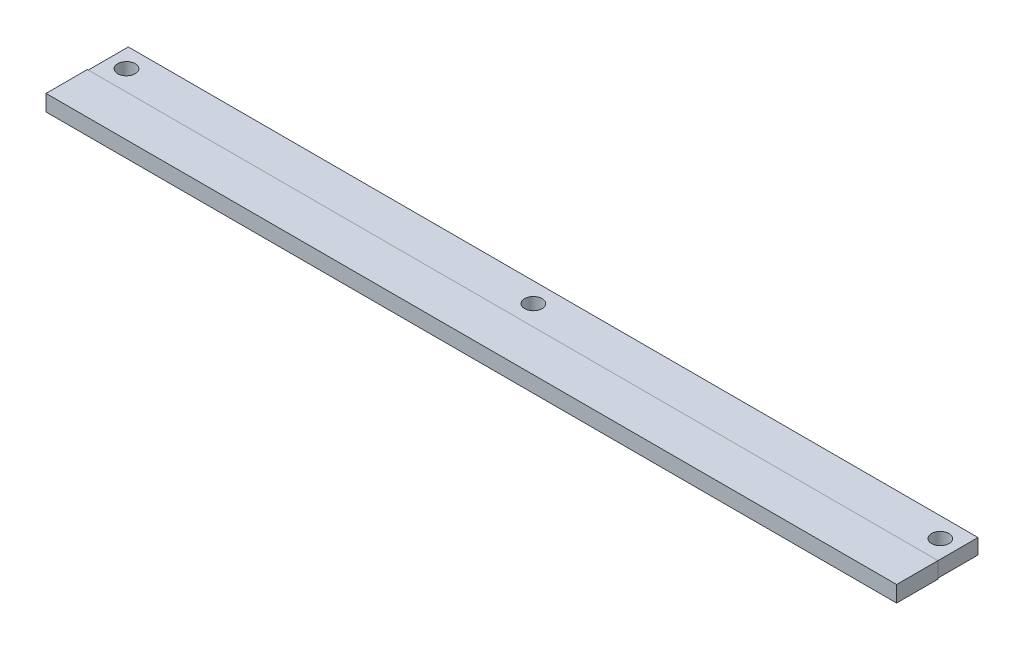
SolidWorks part; units mm, degrees
ref_plane "Front Plane" through (0, 0, 0) normal (1, 0, 0) x (0, 1, 0)
ref_plane "Top Plane" through (0, 0, 0) normal (0, 0, 1) x (0, 1, 0)
ref_plane "Right Plane" through (0, 0, 0) normal (0, 1, 0) x (-1, 0, 0)
sketch "Sketch1" plane through (0, 0, 0) normal (0, 0, 1) x (0, 1, 0)
  line L1 (0, 0) -> (3.5, 0)
  line L2 (0, 0) -> (0, 185)
  line L3 (0, 185) -> (3.5, 185)
  line L4 (3.5, 0) -> (3.5, 185)
  dimension "D1" = 185
  dimension "D2" = 3.5
extrude "Boss-Extrude1" add sketch "Sketch1" along normal blind 18 contours L2 L1 L4 L3
sketch "Sketch2" plane through (0, 3.5, 0) normal (0, 1, 0) x (-1, 0, 0)
  line L1 (185, 0) -> (181, 0)
  line L2 (185, 0) -> (185, 4.5)
  line L3 (185, 4.5) -> (181, 4.5)
  line L4 (181, 0) -> (181, 4.5)
  circle A0 centre (181, 4.5) radius 1.9
  dimension "D3" = 3.8
  dimension "D1" = 4
  dimension "D2" = 4.5
extrude "Cut-Extrude1" cut sketch "Sketch2" against normal up to next contours A0
pattern_linear "LPattern1" count 3 spacing 88.5 along (1, 0, 0) of "Cut-Extrude1"
ref_plane "Plane1" through (0, 0, 9) normal (0, 0, -1) x (-1, 0, 0)
mirror "Mirror1" [suppressed] about plane through (0, 0, 9) normal (0, 0, -1)
sketch "Sketch3" plane through (0, 0, 0) normal (0, 0, -1) x (1, 0, 0)
  line L0 (-184.9, -0.1) -> (-184.9, -3.4)
  line L1 (-185, 0) -> (0, 0)
  line L2 (-185, 0) -> (-185, -3.5)
  line L3 (-185, -3.5) -> (0, -3.5)
  line L4 (0, 0) -> (0, -3.5)
  line L5 (-184.9, -3.4) -> (-0.1, -3.4)
  line L6 (-0.1, -0.1) -> (-0.1, -3.4)
  line L7 (-184.9, -0.1) -> (-0.1, -0.1)
  dimension "D1" = 0.1
extrude "Cut-Extrude2" cut sketch "Sketch3" against normal blind 9
sketch "Sketch5" plane through (0, 3.4, 0) normal (0, 1, 0) x (-1, 0, 0)
  line L0 (0.1, 9) -> (0.1, 0) construction
  line L1 (184.9, 0) -> (0.1, 0)
  line L2 (184.9, 0) -> (184.9, 0.2)
  line L3 (184.9, 0.2) -> (0.1, 0.2)
  line L4 (0.1, 0) -> (0.1, 0.2)
  dimension "D1" = 0.2
extrude "Cut-Extrude3" cut sketch "Sketch5" against normal up to next
equation "\"whitekey_cutout_length\"= 101.5"
equation "\"wall_thickness\"=10"
equation "\"base_mount_height\"=40"
equation "\"base_rear_length\"=80"
equation "\"D1@Sketch1\"=\"base_rear_length\"+\"base_front_length\"-\"dowel_recess_offset\"*2"
equation "\"D2@Sketch1\"=\"wall_thickness\"-\"dowel_recess_offset\"*2"
equation "\"dowel_recess_offset\"=3.25"
equation "\"guide_brace_height\"=20"
equation "\"guide_brace_thickness\"=2"
equation "\"dowel_recess_depth\"=9"
equation "\"base_front_length\"=111.5"
equation "\"screw_hole_wall_offset\"=7.25"
equation "\"screw_hole_edge_inset\"=4.5"
equation "\"screw_hole_diameter\"=3.8"
equation "\"screw_head_hole_diameter\"=6.7"
equation "\"screw_nut_hole_side_len\"=3.5"
equation "\"D1@Boss-Extrude1\"=\"dowel_recess_depth\"*2"
equation "\"D2@Sketch2\"=\"screw_hole_edge_inset\""
equation "\"D1@Sketch2\"=\"screw_hole_wall_offset\"-\"dowel_recess_offset\""
equation "\"D3@Sketch2\"=\"screw_hole_diameter\""
equation "\"D3@LPattern1\"=0.5*(\"base_front_length\"+\"base_rear_length\"-\"screw_hole_wall_offset\"*2)"
equation "\"D1@Cut-Extrude2\"=\"dowel_recess_depth\""
equation "\"key_mount_recess_length\"=50"
equation "\"key_mount_recess_height\"=12.5"
equation "\"key_mount_recess_depth\"=1.5"
equation "\"screw_shaft_diameter\"=3.5"
equation "\"switch_board_width\"=30"
